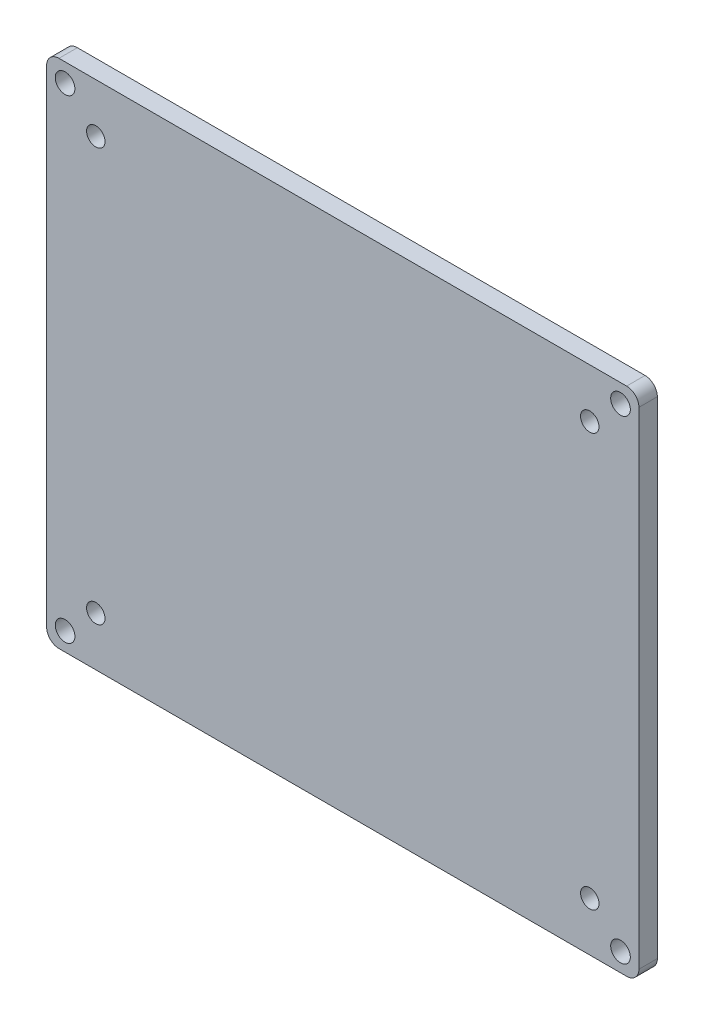
SolidWorks part; units mm, degrees
ref_plane "前视基准面" through (0, 0, 0) normal (0, 0, 1) x (1, 0, 0)
ref_plane "上视基准面" through (0, 0, 0) normal (0, 1, 0) x (1, 0, 0)
ref_plane "右视基准面" through (0, 0, 0) normal (1, 0, 0) x (0, 0, -1)
other "Configuration Table"
sketch "草图1" plane through (0, 0, 0) normal (0, 0, 1) x (1, 0, 0)
  line L0 (45.2, 38.6) -> (45.2, -38.6) construction
  line L1 (40.2, 33.6) -> (-40.2, 33.6)
  line L2 (40.2, 33.6) -> (40.2, -33.6)
  line L3 (40.2, -33.6) -> (-40.2, -33.6)
  line L4 (-40.2, 33.6) -> (-40.2, -33.6)
  line L5 (45.2, -38.6) -> (-45.2, -38.6) construction
  line L6 (-45.2, 38.6) -> (-45.2, -38.6) construction
  line L7 (45.2, 38.6) -> (-45.2, 38.6) construction
  line L8 (48.2, 41.6) -> (48.2, -41.6)
  line L9 (48.2, -41.6) -> (-48.2, -41.6)
  line L10 (-48.2, 41.6) -> (-48.2, -41.6)
  line L11 (48.2, 41.6) -> (-48.2, 41.6)
  circle A1 centre (40.2, -33.6) radius 1.5
  circle A2 centre (40.2, -33.6) radius 1.5
  circle A3 centre (-40.2, -33.6) radius 1.5
  circle A4 centre (-40.2, -33.6) radius 1.5
  circle A5 centre (-40.2, 33.6) radius 1.5
  circle A6 centre (-40.2, 33.6) radius 1.5
  circle A7 centre (40.2, 33.6) radius 1.5
  circle A8 centre (40.2, 33.6) radius 1.5
  circle A9 centre (45.2, 38.6) radius 1.6
  circle A10 centre (45.2, -38.6) radius 1.6
  circle A11 centre (-45.2, 38.6) radius 1.6
  circle A12 centre (-45.2, -38.6) radius 1.6
  dimension "D6" = 3.2
  dimension "D7" = 8
  dimension "D1" = 0
  dimension "D2" = 0
  dimension "D3" = 0
  dimension "D4" = 0
  dimension "D5" = 5
extrude "凸台-拉伸1" add sketch "草图1" along normal blind 3 contours L8 L11 L10 L9 A12 A11 A10 A9 A8 L2 A2 L3 A4 L4 A6 L1 | A8 L1 A6 L4 A4 L3 A2 L2 | L1 A6 L4 | L2 A8 L1 | L1 A8 L2 | L4 A6 L1 | L4 A4 L3 | L3 A4 L4 | L2 A2 L3 | L3 A2 L2 region at (-39.5634, 32.9634, 0) region at (-40.4122, 33.8122, 0) region at (0, 0, 0) region at (40.4122, 33.8122, 0) region at (39.5634, 32.9634, 0) region at (-39.5634, -32.9634, 0) region at (-40.4122, -33.8122, 0) region at (40.4122, -33.8122, 0) region at (39.5634, -32.9634, 0) region at (46.9266, 0, 0)
fillet "圆角1" radius 2 4 edges at (48.2, -41.6, 1.5) (-48.2, -41.6, 1.5) (-48.2, 41.6, 1.5) (48.2, 41.6, 1.5)
extrude "切除-拉伸3" cut sketch "草图1<3>" along normal blind 3 contours L2 A8 L1 | L1 A8 L2 | L3 A2 L2 | L2 A2 L3 | L4 A4 L3 | L3 A4 L4 | L1 A6 L4 | L4 A6 L1 region at (-39.5634, 32.9634, 0) region at (-40.4122, 33.8122, 0) region at (40.4122, 33.8122, 0) region at (39.5634, 32.9634, 0) region at (-39.5634, -32.9634, 0) region at (-40.4122, -33.8122, 0) region at (40.4122, -33.8122, 0) region at (39.5634, -32.9634, 0)
sketch "草图1<3>" plane through (0, 0, 0) normal (0, 0, 1) x (1, 0, 0) same geometry as "草图1"
